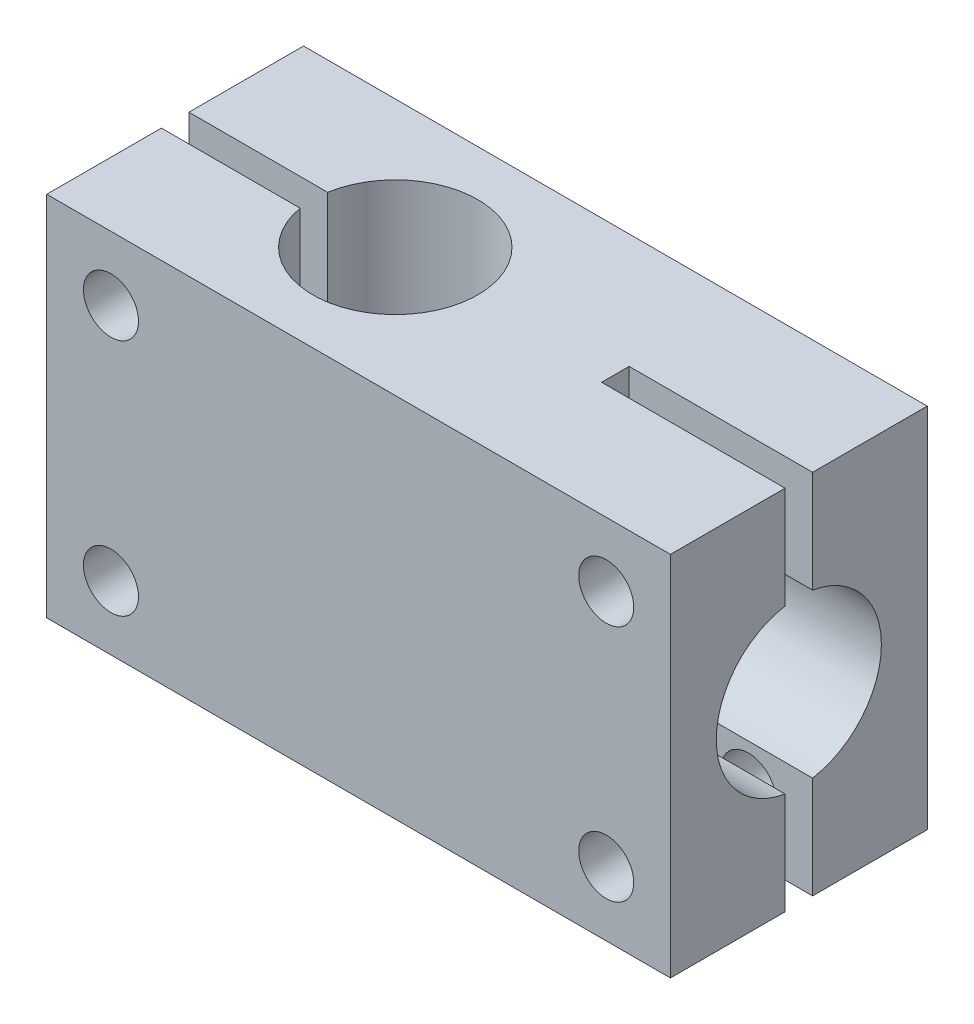
SolidWorks part; units mm, degrees
ref_plane "Front Plane" through (0, 0, 0) normal (0, 0, 1) x (1, 0, 0)
ref_plane "Top Plane" through (0, 0, 0) normal (0, 1, 0) x (1, 0, 0)
ref_plane "Right Plane" through (0, 0, 0) normal (1, 0, 0) x (0, 0, -1)
sketch "Sketch1" plane through (0, 0, 0) normal (0, 1, 0) x (1, 0, 0)
  line L0 (-48.5333, 0) -> (43.702, 0) construction
  line L1 (0, 34.3137) -> (0, -30.6902) construction
  line L2 (-17, 0) -> (-17, 14)
  line L3 (-17, 14) -> (17, 14)
  line L4 (-17, 0) -> (17, 0)
  line L5 (17, 0) -> (17, 14)
  point P10 (0, 0)
  point P11 (0, 14)
  dimension "D1" = 14
  dimension "D2" = 17
extrude "Boss-Extrude2" add sketch "Sketch1" along normal blind 20
sketch "Sketch3" plane through (0, 20, 0) normal (0, 1, 0) x (1, 0, 0)
  line L0 (17, 14) -> (-17, 14) construction
  line L1 (-17, 14) -> (-17, 0) construction
  line L2 (-26.2064, 7) -> (19.291, 7) construction
  line L3 (-9.4371, 7.75) -> (-17, 7.75)
  line L4 (-17, 7.75) -> (-17, 7)
  line L5 (-9.4371, 6.25) -> (-17, 6.25)
  line L6 (-17, 6.25) -> (-17, 7)
  circle A0 centre (-5, 7) radius 4.5
  arc A1 (-9.4371, 7.75) -> (-9.4371, 6.25) centre (-5, 7) ccw
  line M8 (-17, 14) -> (-17, 0)
  dimension "D1" = 7
  dimension "D2" = 12
  dimension "D3" = 9
  dimension "D4" = 0.75
  dimension "D5" = 0.75
extrude "Cut-Extrude1" cut sketch "Sketch3" against normal through all contours L2 A1 A0 | A0 L2 | L2 A0 L3 M8 | L2 L5 A1 M8 region at (-13.2395, 20, -7.3755) region at (-13.2395, 20, -6.6245) region at (-5, 20, -8.9099) region at (-5, 20, -5.0901)
sketch "Sketch4" plane through (17, 0, 0) normal (1, 0, 0) x (0, 0, -1)
  line L0 (0, 20) -> (14, 20) construction
  line L1 (14, 20) -> (14, 0) construction
  line L2 (6.999, 21.0943) -> (6.999, -3.7951) construction
  line L3 (-5.0984, 10) -> (23.1605, 10) construction
  line L4 (7.749, 14.4371) -> (7.749, 20)
  line L5 (7.749, 20) -> (7, 20)
  line L6 (6.249, 14.4371) -> (6.249, 20)
  line L7 (6.249, 20) -> (7, 20)
  line L8 (6.249, 0) -> (7, 0)
  line L9 (7.749, 0) -> (7, 0)
  line L10 (6.249, 5.5629) -> (6.249, 0)
  line L11 (7.749, 5.5629) -> (7.749, 0)
  circle A0 centre (6.999, 10) radius 4.5
  arc A1 (7.749, 14.4371) -> (6.249, 14.4371) centre (6.999, 10) cw
  arc A2 (6.249, 5.5629) -> (7.749, 5.5629) centre (6.999, 10) ccw
  line M4 (14, 20) -> (0, 20)
  dimension "D1" = 9
  dimension "D2" = 10
  dimension "D3" = 7.001
  dimension "D4" = 0.75
  dimension "D5" = 0.75
extrude "Cut-Extrude2" cut sketch "Sketch4" against normal blind 10 contours A0 | A0 L4 L6 M4 | L11 L9 L8 L10 A2 region at (17, 17.2395, -6.999) region at (17, 10, -6.999)
sketch "Sketch5" plane through (0, 0, 0) normal (0, 0, 1) x (1, 0, 0)
  line L0 (-17, 20) -> (17, 20) construction
  line L1 (-17, 20) -> (-17, 0) construction
  line L2 (17, 20) -> (17, 0) construction
  line L3 (-17, 0) -> (17, 0) construction
  circle A0 centre (-13.5, 16.5) radius 1.5
  circle A1 centre (-13.5, 3.5) radius 1.5
  circle A2 centre (13.5, 16.5) radius 1.5
  circle A3 centre (13.5, 3.5) radius 1.5
  dimension "D1" = 3
  dimension "D2" = 3.5
  dimension "D3" = 3.5
  dimension "D4" = 3.5
  dimension "D5" = 3.5
  dimension "D6" = 3.5
  dimension "D7" = 3.5
  dimension "D8" = 3.5
  dimension "D9" = 3.5
extrude "Cut-Extrude4" cut sketch "Sketch5" against normal through all
